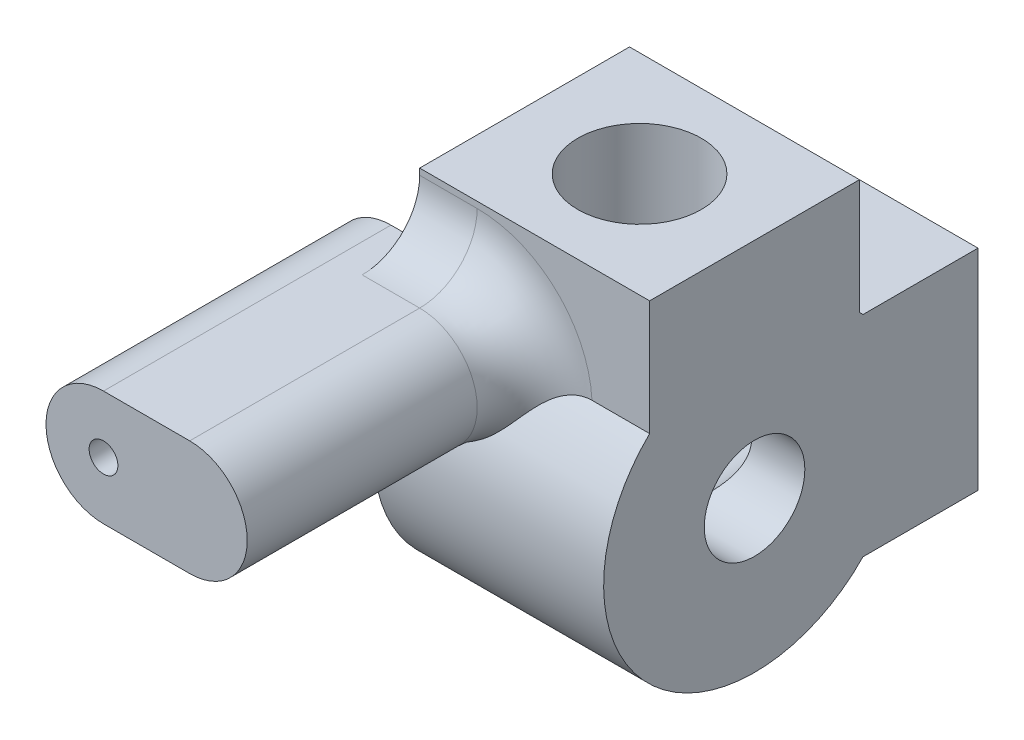
SolidWorks part; units mm, degrees
material "PLA Black"
ref_plane "Front" through (0, 0, 0) normal (0, 0, 1) x (1, 0, 0)
ref_plane "Top" through (0, 0, 0) normal (0, 1, 0) x (1, 0, 0)
ref_plane "Right" through (0, 0, 0) normal (1, 0, 0) x (0, 0, -1)
sketch "Sketch1" plane through (0, 0, 0) normal (1, 0, 0) x (0, 0, -1)
  line L0 (1.118, 1) -> (-1.118, 1) construction
  line L1 (-3.65, 3.7736) -> (3.65, 3.7736)
  line L2 (3.7736, 3.65) -> (3.7736, -3.65)
  line L3 (0, 0) -> (11.6334, 0) construction
  line L4 (0, 0) -> (0, 8.6732) construction
  arc A0 (-1.118, 1) -> (1.118, 1) centre (0, 0) ccw construction
  circle A1 centre (0, 0) radius 1.75
  arc A2 (3.7736, -3.65) -> (-3.65, 3.7736) centre (0, 0) cw
  arc A3 (3.7736, 3.65) -> (3.65, 3.7736) centre (0, 0) ccw
  dimension "D1" = 3
  dimension "D3" = 0.25
  dimension "D5" = 3.5
  dimension "D2" = 1
  dimension "D4" = 7.3
extrude "Boss-Extrude1" add sketch "Sketch1" along normal mid plane 8
sketch "Sketch2" plane through (0, 3.7736, 0) normal (0, 1, 0) x (1, 0, 0)
  circle A0 centre (0, 0) radius 2.15
  dimension "D1" = 4.3
extrude "Cut-Extrude1" cut sketch "Sketch2" against normal blind 5
sketch "Sketch3" plane through (0, 0, -3.7736) normal (0, 0, -1) x (-1, 0, 0)
  circle A0 centre (0, 0) radius 2.15
  dimension "D1" = 4.3
extrude "Cut-Extrude2" cut sketch "Sketch3" against normal blind 5
sketch "Sketch4" plane through (0, 3.7736, 0) normal (0, 1, 0) x (1, 0, 0)
  line L0 (4, 3.65) -> (-4, 3.65) construction
  line L1 (4, 3.65) -> (4, -3.65) construction
  line L2 (4, -3.65) -> (-4, -3.65) construction
  line L3 (-4, 3.65) -> (-4, -3.65) construction
  line L4 (4, 3.65) -> (-4, 3.65)
  line L5 (4, 3.65) -> (4, -3.65)
  line L6 (4, -3.65) -> (-4, -3.65)
  line L7 (-4, 3.65) -> (-4, -3.65)
  circle A0 centre (0, 0) radius 2.15 construction
  circle A1 centre (0, 0) radius 2.15
extrude "Boss-Extrude2" add sketch "Sketch4" along normal blind 4
sketch "Sketch5" plane through (0, 0, -3.7736) normal (0, 0, -1) x (-1, 0, 0)
  line L0 (-4, 3.65) -> (4, 3.65) construction
  line L1 (4, -3.65) -> (4, 3.65) construction
  line L2 (-4, -3.65) -> (4, -3.65) construction
  line L3 (-4, -3.65) -> (-4, 3.65) construction
  line L4 (-4, 3.65) -> (4, 3.65)
  line L5 (4, -3.65) -> (4, 3.65)
  line L6 (-4, -3.65) -> (4, -3.65)
  line L7 (-4, -3.65) -> (-4, 3.65)
  circle A0 centre (0, 0) radius 2.15 construction
  circle A1 centre (0, 0) radius 2.15
extrude "Boss-Extrude3" add sketch "Sketch5" along normal blind 4
ref_axis "Axis1" through (4, 0, 0) along (-1, 0, 0)
sketch "Sketch6" plane through (0, 0, 3.65) normal (0, 0, 1) x (1, 0, 0)
  line L0 (-4, 7.7736) -> (-4, 3.7736) construction
  line L2 (-2, 5.555) -> (-5, 5.555)
  line L3 (-5, 1.555) -> (-2, 1.555)
  line L6 (4, 0) -> (-4, 0) construction
  circle A0 centre (-5, 3.555) radius 0.5
  arc A1 (-5, 5.555) -> (-5, 1.555) centre (-5, 3.555) ccw
  arc A2 (-2, 5.555) -> (-2, 1.555) centre (-2, 3.555) cw
  dimension "D1" = 1
  dimension "D2" = 3.555
  dimension "D3" = 1.5
  dimension "D4" = 1
  dimension "D5" = 3
extrude "Boss-Extrude4" add sketch "Sketch6" along normal blind 10
fillet "Fillet1" radius 2 2 edges at (-0.6653, 5.0445, 3.65) (-3, 5.555, 3.65)
equation "\"knee_angle\"= 90"
equation "\"ankle_angle\" = 80"
equation "\"hip_angle\" = 30"
equation "\"spring_ankle_parallel_arm_diameter\"= 0.43"
equation "\"spring_ankle_parallel_arm_length\"= 15"
equation "\"spring_ankle_parallel_intern_diameter\"= 5.46"
equation "\"spring_ankle_parallel_angle\"= \"ankle_angle\""
equation "\"spring_ankle_parallel_turns\"= 3"
equation "\"spring_ankle_parallel_pitch\"= \"spring_ankle_parallel_arm_diameter\" * 1.01"
equation "\"spring_ankle_parallel_cutting_distance\"= (1-\"spring_ankle_parallel_angle\" / 360) * \"spring_ankle_parallel_pitch\""
equation "\"spring_ankle_serial_arm_diameter\"= 0.89"
equation "\"spring_ankle_serial_arm_length\"= 10"
equation "\"spring_ankle_serial_intern_diameter\"= 6.22"
equation "\"spring_ankle_serial_angle\"= \"90\""
equation "\"spring_ankle_serial_turns\"= 3"
equation "\"spring_ankle_serial_pitch\"= \"spring_ankle_serial_arm_diameter\" * 1.01"
equation "\"spring_ankle_serial_cutting_distance\"= (1-\"spring_ankle_serial_angle\" / 360) * \"spring_ankle_serial_pitch\""
equation "\"spring_knee_parallel_arm_diameter\"= 0.43"
equation "\"spring_knee_parallel_arm_length\"= 15"
equation "\"spring_knee_parallel_intern_diameter\"= 5.46"
equation "\"spring_knee_parallel_angle\"= \"knee_angle\""
equation "\"spring_knee_parallel_turns\"= 3"
equation "\"spring_knee_parallel_pitch\"= \"spring_knee_parallel_arm_diameter\" * 1.01"
equation "\"spring_knee_parallel_cutting_distance\"= (1-\"spring_knee_parallel_angle\" / 360) * \"spring_knee_parallel_pitch\""
equation "\"spring_knee_serial_arm_diameter\"= 0.43"
equation "\"spring_knee_serial_arm_length\"= 10"
equation "\"spring_knee_serial_intern_diameter\"= 5.46"
equation "\"spring_knee_serial_angle\"= \"90\""
equation "\"spring_knee_serial_turns\"= 3"
equation "\"spring_knee_serial_pitch\"= \"spring_knee_serial_arm_diameter\" * 1.01"
equation "\"spring_knee_serial_cutting_distance\"= (1-\"spring_knee_serial_angle\" / 360) * \"spring_knee_serial_pitch\""
equation "\"D2@Sketch6\"=(\"spring_ankle_serial_intern_diameter\" + \"spring_ankle_serial_arm_diameter\")/2"
